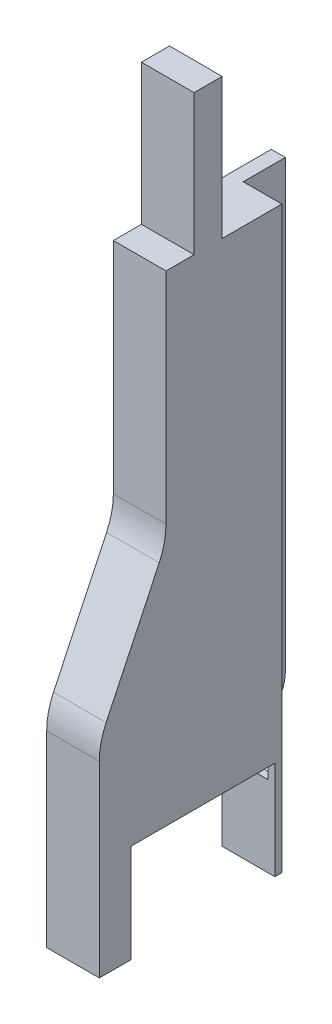
SolidWorks part; units mm, degrees
ref_plane "정면" through (0, 0, 0) normal (0, 0, 1) x (1, 0, 0)
ref_plane "윗면" through (0, 0, 0) normal (0, 1, 0) x (1, 0, 0)
ref_plane "우측면" through (0, 0, 0) normal (1, 0, 0) x (0, 0, -1)
sketch "스케치1" plane through (0, 0, 0) normal (0, 0, 1) x (1, 0, 0)
  line L0 (-318.5049, 0) -> (318.5049, 0) construction
  line L1 (0, 0) -> (0, -258.8265) construction
  line L2 (-168, 0) -> (168, 0)
  line L3 (-168, -20) -> (168, -20)
  line L4 (168, -20) -> (168, 0) construction
  line L5 (168, -20) -> (168, -340)
  line L6 (172, -340) -> (172, 0)
  line L7 (168, 0) -> (183, 0)
  line L8 (183, 0) -> (183, -340)
  line L9 (183, -340) -> (168, -340)
  line L10 (-168, -20) -> (-168, 0) construction
  line L11 (-183, -340) -> (-168, -340)
  line L12 (-183, 0) -> (-183, -340)
  line L13 (-168, 0) -> (-183, 0)
  line L14 (-172, -340) -> (-172, 0)
  line L15 (-168, -20) -> (-168, -340)
  line L16 (168, -20) -> (168, 0)
  line L17 (-168, -20) -> (-168, 0)
  point P14 (0, -20)
  dimension "D1" = 168
  dimension "D2" = 20
  dimension "D3" = 4
  dimension "D4" = 340
  dimension "D5" = 15
extrude "보스-돌출1" add sketch "스케치1" along normal blind 26 contours L3 L5 L9 L8 L7 L2 L13 L12 L11 L15
extrude "보스-돌출2" add sketch "스케치1<4>" against normal blind 19 contours L16 L5 L9 L6 L7 | L15 L17 L13 L14 L11 region at (-170, -170, 0) region at (170, -170, 0)
sketch "스케치1<4>" plane through (0, 0, 0) normal (0, 0, 1) x (1, 0, 0) same geometry as "스케치1"
fillet "필렛1" radius 10 4 edges at (-170, 0, -19) (170, 0, -19) (170, -340, -19) (-170, -340, -19)
sketch "스케치2" plane through (172, 0, 0) normal (1, 0, 0) x (0, 0, -1)
  line L0 (14, -340) -> (14, 0)
  line L1 (12, 0) -> (12, -340)
  line L4 (19, -330) -> (19, -10)
  line L5 (9, 0) -> (0, 0)
  line L6 (0, 0) -> (0, -340)
  line L7 (0, -340) -> (9, -340)
  line L8 (19, -330) -> (19, -10)
  line L9 (9, 0) -> (0, 0)
  line L10 (0, 0) -> (0, -340)
  line L11 (0, -340) -> (9, -340)
  arc A2 (19, -10) -> (9, 0) centre (9, -10) ccw
  arc A3 (9, -340) -> (19, -330) centre (9, -330) ccw
  arc A4 (19, -10) -> (9, 0) centre (9, -10) ccw
  arc A5 (9, -340) -> (19, -330) centre (9, -330) ccw
  dimension "D2" = 5
  dimension "D3" = 2
  dimension "D1" = 0
sketch "스케치3" plane through (168, 0, 0) normal (-1, 0, 0) x (0, 0, 1)
  line L0 (-12, 0) -> (-12, -340) construction
  line L1 (-14, -340) -> (-14, 0) construction
  line L2 (-12, 0) -> (-12, -340)
  line L3 (-14, -340) -> (-14, 0)
  line L4 (-19, -10) -> (-19, -330)
  line L5 (0, 0) -> (-9, 0)
  line L6 (0, -340) -> (0, 0)
  line L7 (-9, -340) -> (0, -340)
  line L8 (-19, -10) -> (-19, -330)
  line L9 (0, 0) -> (-9, 0)
  line L10 (0, -340) -> (0, 0)
  line L11 (-9, -340) -> (0, -340)
  arc A2 (-9, 0) -> (-19, -10) centre (-9, -10) ccw
  arc A3 (-19, -330) -> (-9, -340) centre (-9, -330) ccw
  arc A4 (-9, 0) -> (-19, -10) centre (-9, -10) ccw
  arc A5 (-19, -330) -> (-9, -340) centre (-9, -330) ccw
  dimension "D1" = 0
sketch "스케치5" plane through (0, 0, 0) normal (0, 1, 0) x (1, 0, 0)
  line L0 (-7, 0) -> (-7, -26)
  line L1 (7, 0) -> (7, -26)
  line L2 (-168, 0) -> (-168, -6)
  line L3 (-168, -6) -> (-7, -6)
  line L4 (7, -6) -> (168, -6)
  line L5 (168, -6) -> (168, 0)
  line L12 (-168, 0) -> (-168, 9)
  line L13 (-168, 9) -> (-172, 9)
  line L14 (-172, 9) -> (-172, 0)
  line L15 (-172, 0) -> (-183, 0)
  line L16 (-183, 0) -> (-183, -26)
  line L17 (-183, -26) -> (183, -26)
  line L18 (183, -26) -> (183, 0)
  line L19 (183, 0) -> (172, 0)
  line L20 (172, 0) -> (172, 9)
  line L21 (172, 9) -> (168, 9)
  line L22 (168, 9) -> (168, 0)
  line L23 (168, 0) -> (-168, 0)
  line L24 (-168, 0) -> (-168, 9)
  line L25 (-168, 9) -> (-172, 9)
  line L26 (-172, 9) -> (-172, 0)
  line L27 (-172, 0) -> (-183, 0)
  line L28 (-183, 0) -> (-183, -26)
  line L29 (-183, -26) -> (183, -26)
  line L30 (183, -26) -> (183, 0)
  line L31 (183, 0) -> (172, 0)
  line L32 (172, 0) -> (172, 9)
  line L33 (172, 9) -> (168, 9)
  line L34 (168, 9) -> (168, 0)
  line L35 (168, 0) -> (-168, 0)
  line M27 (168, 0) -> (-168, 0)
  dimension "D2" = 7
  dimension "D3" = 7
  dimension "D4" = 6
  dimension "D1" = 0
extrude "컷-돌출1" cut sketch "스케치5" against normal blind 52 contours L2 L3 L0 M27 | L4 L5 L1 M27 region at (-87.5, 0, 3) region at (87.5, 0, 3)
extrude "보스-돌출4" add sketch "스케치1<5>" against normal blind 7 contours L9 L8 L7 L6 | L11 L14 L13 L12 region at (-177.5, -170, 0) region at (177.5, -170, 0)
sketch "스케치1<5>" plane through (0, 0, 0) normal (0, 0, 1) x (1, 0, 0) same geometry as "스케치1"
sketch "스케치6" plane through (0, -340, 0) normal (0, -1, 0) x (1, 0, 0)
  line L0 (-172, -7) -> (-126.7636, -7) construction
  line L1 (-172, -7) -> (-168, -7)
  line L2 (-168, -7) -> (-168, -5)
  line L3 (-168, -5) -> (-174.5, -5)
  line L4 (-174.5, -5) -> (-174.5, -7)
  line L5 (-181.1, -7) -> (-181.1, -5)
  line L6 (-172, -7) -> (-172, -9)
  line L7 (-172, -9) -> (-168, -9)
  line L8 (-168, -9) -> (-168, 26)
  line L9 (-168, 26) -> (-183, 26)
  line L10 (-183, 26) -> (-183, -7)
  line L11 (-183, -7) -> (-172, -7)
  line L12 (-172, -7) -> (-172, -9)
  line L13 (-172, -9) -> (-168, -9)
  line L14 (-168, -9) -> (-168, 26)
  line L15 (-168, 26) -> (-183, 26)
  line L16 (-183, 26) -> (-183, -7)
  line L17 (-183, -7) -> (-172, -7)
  line L18 (-181.1, -5) -> (-183, -5)
  line L19 (-181.1, -5) -> (-174.5, -5)
  line L20 (-168, 26) -> (-168, 36)
  line L21 (-168, 36) -> (-183, 36)
  line L22 (-183, 36) -> (-183, 26)
  line L23 (-168, 36) -> (-168, 45)
  line L24 (-168, 45) -> (-183, 45)
  line L25 (-183, 45) -> (-183, 36)
  line M14 (-168, -9) -> (-168, 26)
  line M15 (-168, 26) -> (-183, 26)
  line M17 (-183, -7) -> (-172, -7)
  dimension "D2" = 6.5
  dimension "D3" = 2
  dimension "D4" = 6.6
  dimension "D5" = 41
  dimension "D6" = 9
  dimension "D1" = 0
extrude "보스-돌출5" add sketch "스케치6" along normal blind 28 contours L5 L18 L16 M17 | L19 L5 L4 M17 | L3 L4 L1 M17 M14 region at (-171.25, -340, -6) region at (-177.8, -340, -6) region at (-182.05, -340, -6)
extrude "컷-돌출2" cut sketch "스케치6<3>" along normal blind 5 contours L19 L5 L4 M17 region at (-177.8, -340, -6)
sketch "스케치6<3>" plane through (0, -340, 0) normal (0, -1, 0) x (1, 0, 0) same geometry as "스케치6"
fillet "필렛2" radius 20 1 edges at (-170, -340, -7)
extrude "보스-돌출6" add sketch "스케치6<4>" against normal blind 30 contours L21 L22 L20 M15 | L24 L25 L21 L23 region at (-175.5, -340, 31) region at (-175.5, -340, 40.5)
sketch "스케치6<4>" plane through (0, -340, 0) normal (0, -1, 0) x (1, 0, 0) same geometry as "스케치6"
extrude "보스-돌출7" add sketch "스케치6<5>" along normal blind 28 contours L24 L25 L21 L23 region at (-175.5, -340, 40.5)
sketch "스케치6<5>" plane through (0, -340, 0) normal (0, -1, 0) x (1, 0, 0) same geometry as "스케치6"
sketch "스케치9" plane through (-183, 0, 0) normal (-1, 0, 0) x (0, 0, 1)
  line L0 (45, -310) -> (26, -270)
  line L1 (26, 0) -> (26, -310) construction
  line L12 (26, 0) -> (-7, 0)
  line L13 (-7, 0) -> (-7, -368)
  line L14 (-7, -368) -> (-5, -368)
  line L15 (-5, -368) -> (-5, -340)
  line L16 (-5, -340) -> (36, -340)
  line L17 (36, -340) -> (36, -368)
  line L18 (36, -368) -> (45, -368)
  line L19 (45, -368) -> (45, -310)
  line L20 (45, -310) -> (26, -310)
  line L21 (26, -310) -> (26, 0)
  line L22 (26, 0) -> (-7, 0)
  line L23 (-7, 0) -> (-7, -368)
  line L24 (-7, -368) -> (-5, -368)
  line L25 (-5, -368) -> (-5, -340)
  line L26 (-5, -340) -> (36, -340)
  line L27 (36, -340) -> (36, -368)
  line L28 (36, -368) -> (45, -368)
  line L29 (45, -368) -> (45, -310)
  line L30 (45, -310) -> (26, -310)
  line L31 (26, -310) -> (26, 0)
  line M19 (45, -310) -> (26, -310)
  line M20 (26, -310) -> (26, 0)
  dimension "D2" = 40
  dimension "D1" = 0
extrude "보스-돌출8" add sketch "스케치9" against normal blind 15 contours L0 M19 M20 region at (-183, -296.6667, 32.3333)
fillet "필렛3" radius 20 2 edges at (-175.5, -270, 26) (-175.5, -310, 45)
mirror "대칭 복사2" about plane through (0, 0, 0) normal (1, 0, 0) of "보스-돌출5", "컷-돌출2", "필렛3", "보스-돌출6", "보스-돌출7", "보스-돌출8"
fillet "필렛4" radius 20 1 edges at (170, -340, -7)
sketch "스케치10" plane through (183, 0, 0) normal (1, 0, 0) x (0, 0, -1)
  line L0 (-27.9344, -274.0725) -> (-43.0656, -305.9275) construction
  line L1 (-45, -314.5086) -> (-45, -368) construction
  line L2 (-45, -368) -> (-36, -368) construction
  line L3 (-36, -368) -> (-36, -340) construction
  line L4 (-36, -340) -> (5, -340) construction
  line L5 (5, -340) -> (5, -368) construction
  line L6 (5, -368) -> (7, -368) construction
  line L7 (7, -368) -> (7, -354) construction
  line L8 (19, -330) -> (19, -10) construction
  line L9 (9, 0) -> (-6, 0) construction
  line L10 (-6, 0) -> (-6, -20) construction
  line L11 (-6, -20) -> (-26, -20) construction
  line L12 (-26, -20) -> (-26, -265.4914) construction
  line L13 (-27.9344, -274.0725) -> (-43.0656, -305.9275) construction
  line L14 (-45, -314.5086) -> (-45, -368) construction
  line L15 (-45, -368) -> (-36, -368) construction
  line L16 (-36, -368) -> (-36, -340) construction
  line L17 (-36, -340) -> (5, -340) construction
  line L18 (5, -340) -> (5, -368) construction
  line L19 (5, -368) -> (7, -368) construction
  line L20 (7, -368) -> (7, 0) construction
  line L21 (7, 0) -> (-26, 0) construction
  line L22 (-26, 0) -> (-26, -265.4914) construction
  line L23 (-27.9344, -274.0725) -> (-43.0656, -305.9275)
  line L24 (-45, -314.5086) -> (-45, -368)
  line L25 (-45, -368) -> (-36, -368)
  line L26 (-36, -368) -> (-36, -340)
  line L27 (-36, -340) -> (5, -340)
  line L28 (5, -340) -> (5, -368)
  line L29 (5, -368) -> (7, -368)
  line L30 (7, -368) -> (7, -354)
  line L31 (19, -330) -> (19, -10)
  line L32 (9, 0) -> (-6, 0)
  line L33 (-6, 0) -> (-6, -20)
  line L34 (-6, -20) -> (-26, -20)
  line L35 (-26, -20) -> (-26, -265.4914)
  line L36 (-27.9344, -274.0725) -> (-43.0656, -305.9275)
  line L37 (-45, -314.5086) -> (-45, -368)
  line L38 (-45, -368) -> (-36, -368)
  line L39 (-36, -368) -> (-36, -340)
  line L40 (-36, -340) -> (5, -340)
  line L41 (5, -340) -> (5, -368)
  line L42 (5, -368) -> (7, -368)
  line L43 (7, -368) -> (7, 0)
  line L44 (7, 0) -> (-26, 0)
  line L45 (-26, 0) -> (-26, -265.4914)
  line L46 (-26, -10) -> (-6, -10)
  arc A0 (-43.0656, -305.9275) -> (-45, -314.5086) centre (-25, -314.5086) ccw construction
  arc A1 (15, -338) -> (7, -354) centre (27, -354) ccw construction
  arc A2 (15, -338) -> (19, -330) centre (9, -330) ccw construction
  arc A3 (19, -10) -> (9, 0) centre (9, -10) ccw construction
  arc A4 (-27.9344, -274.0725) -> (-26, -265.4914) centre (-46, -265.4914) ccw construction
  arc A5 (-43.0656, -305.9275) -> (-45, -314.5086) centre (-25, -314.5086) ccw construction
  arc A6 (-27.9344, -274.0725) -> (-26, -265.4914) centre (-46, -265.4914) ccw construction
  arc A7 (-43.0656, -305.9275) -> (-45, -314.5086) centre (-25, -314.5086) ccw
  arc A8 (15, -338) -> (7, -354) centre (27, -354) ccw
  arc A9 (15, -338) -> (19, -330) centre (9, -330) ccw
  arc A10 (19, -10) -> (9, 0) centre (9, -10) ccw
  arc A11 (-27.9344, -274.0725) -> (-26, -265.4914) centre (-46, -265.4914) ccw
  arc A12 (-43.0656, -305.9275) -> (-45, -314.5086) centre (-25, -314.5086) ccw
  arc A13 (-27.9344, -274.0725) -> (-26, -265.4914) centre (-46, -265.4914) ccw
sketch "스케치11" plane through (168, 0, 0) normal (-1, 0, 0) x (0, 0, 1)
  line L10 (43.0656, -305.9275) -> (27.9344, -274.0725)
  line L11 (45, -368) -> (45, -314.5086)
  line L12 (36, -368) -> (45, -368)
  line L13 (45, -368) -> (45, -314.5086)
  line L14 (43.0656, -305.9275) -> (27.9344, -274.0725)
  line L15 (26, -265.4914) -> (26, -20)
  line L16 (26, -20) -> (6, -20)
  line L17 (6, -20) -> (6, 0)
  line L18 (6, 0) -> (-9, 0)
  line L19 (-19, -10) -> (-19, -330)
  line L20 (-7, -354) -> (-7, -368)
  line L21 (-7, -368) -> (-5, -368)
  line L22 (-5, -368) -> (-5, -340)
  line L23 (-5, -340) -> (36, -340)
  line L24 (36, -340) -> (36, -368)
  line L25 (36, -368) -> (45, -368)
  line L26 (45, -368) -> (45, -314.5086)
  line L27 (43.0656, -305.9275) -> (27.9344, -274.0725)
  line L28 (26, -265.4914) -> (26, -20)
  line L29 (26, -20) -> (6, -20)
  line L30 (6, -20) -> (6, 0)
  line L31 (6, 0) -> (-9, 0)
  line L32 (-19, -10) -> (-19, -330)
  line L33 (-7, -354) -> (-7, -368)
  line L34 (-7, -368) -> (-5, -368)
  line L35 (-5, -368) -> (-5, -340)
  line L36 (-5, -340) -> (36, -340)
  line L37 (36, -340) -> (36, -368)
  line L38 (36, -368) -> (45, -368)
  line L39 (36, -340) -> (36, -368)
  line L40 (-5, -340) -> (36, -340)
  line L41 (-5, -368) -> (-5, -340)
  line L42 (-7, -368) -> (-5, -368)
  line L43 (-7, 0) -> (-7, -368)
  line L44 (26, 0) -> (-7, 0)
  line L45 (26, -265.4914) -> (26, 0)
  line L46 (43.0656, -305.9275) -> (27.9344, -274.0725)
  line L47 (45, -368) -> (45, -314.5086)
  line L48 (36, -368) -> (45, -368)
  line L49 (36, -340) -> (36, -368)
  line L50 (-5, -340) -> (36, -340)
  line L51 (-5, -368) -> (-5, -340)
  line L52 (-7, -368) -> (-5, -368)
  line L53 (-7, 0) -> (-7, -368)
  line L54 (26, 0) -> (-7, 0)
  line L55 (26, -265.4914) -> (26, 0)
  arc A2 (45, -314.5086) -> (43.0656, -305.9275) centre (25, -314.5086) ccw
  arc A3 (26, -265.4914) -> (27.9344, -274.0725) centre (46, -265.4914) ccw
  arc A4 (45, -314.5086) -> (43.0656, -305.9275) centre (25, -314.5086) ccw
  arc A5 (45, -314.5086) -> (43.0656, -305.9275) centre (25, -314.5086) ccw
  arc A6 (26, -265.4914) -> (27.9344, -274.0725) centre (46, -265.4914) ccw
  arc A7 (-9, 0) -> (-19, -10) centre (-9, -10) ccw
  arc A8 (-19, -330) -> (-15, -338) centre (-9, -330) ccw
  arc A9 (-7, -354) -> (-15, -338) centre (-27, -354) ccw
  arc A10 (45, -314.5086) -> (43.0656, -305.9275) centre (25, -314.5086) ccw
  arc A11 (26, -265.4914) -> (27.9344, -274.0725) centre (46, -265.4914) ccw
  arc A12 (-9, 0) -> (-19, -10) centre (-9, -10) ccw
  arc A13 (-19, -330) -> (-15, -338) centre (-9, -330) ccw
  arc A14 (-7, -354) -> (-15, -338) centre (-27, -354) ccw
  arc A15 (26, -265.4914) -> (27.9344, -274.0725) centre (46, -265.4914) ccw
  line M31 (45, -368) -> (45, -314.5086)
  arc M32 (45, -314.5086) -> (43.0656, -305.9275) centre (25, -314.5086) ccw
  line M33 (43.0656, -305.9275) -> (27.9344, -274.0725)
  arc M34 (27.9344, -274.0725) -> (26, -265.4914) centre (46, -265.4914) cw
  line M35 (26, -265.4914) -> (26, -20)
  line M36 (26, -20) -> (6, -20)
  line M37 (6, -20) -> (6, 0)
  line M38 (6, 0) -> (-9, 0)
  arc M39 (-9, 0) -> (-19, -10) centre (-9, -10) ccw
  line M40 (-19, -10) -> (-19, -330)
  arc M41 (-19, -330) -> (-15, -338) centre (-9, -330) ccw
  arc M42 (-15, -338) -> (-7, -354) centre (-27, -354) cw
  line M43 (-7, -354) -> (-7, -368)
  line M44 (-7, -368) -> (-5, -368)
  line M45 (-5, -368) -> (-5, -340)
  line M46 (-5, -340) -> (36, -340)
  line M47 (36, -340) -> (36, -368)
  line M48 (36, -368) -> (45, -368)
  dimension "D1" = 0
  dimension "D2" = 0
extrude "컷-돌출3" cut sketch "스케치11" along normal blind 617 contours L53 M38 M43 M44 M45 M46 M47 M48 M31 M32 M33 M34 M35 M36 M37 | L55 L54 M36 M37 | L53 L31 M39 M40 M41 M42 region at (168, -191.2863, 11.8028) region at (168, -10, 16) region at (168, -171.1237, -12.9334)
extrude "컷-돌출4" cut sketch "스케치10" against normal blind 617 contours L46 L45 L34 L33 region at (183, -15, 16)
sketch "스케치12" plane through (168, 0, 0) normal (-1, 0, 0) x (0, 0, 1)
  line L0 (18, -203) -> (18, -163)
  line L1 (18, -163) -> (10, -163)
  line L2 (10, -163) -> (10, -203)
  line L3 (10, -203) -> (-19, -203)
  line L4 (18.5, -203) -> (18.5, -162.5)
  line L5 (18.5, -162.5) -> (9.5, -162.5)
  line L6 (9.5, -162.5) -> (9.5, -203)
  line L15 (26, -183) -> (-19, -183) construction
  line L16 (26, -203) -> (18, -203)
  line L18 (-7, 0) -> (-9, 0)
  line L19 (-7, -354) -> (-7, 0)
  line L20 (-19, -10) -> (-19, -330)
  line L21 (-7, 0) -> (-9, 0)
  line L22 (-7, -354) -> (-7, 0)
  line L23 (-19, -10) -> (-19, -330)
  line L30 (6, -10) -> (26, -10)
  line L31 (26, -10) -> (26, 0)
  line L32 (26, 0) -> (-9, 0)
  line L33 (-19, -10) -> (-19, -330)
  line L34 (-7, -354) -> (-7, -368)
  line L35 (-7, -368) -> (-5, -368)
  line L36 (-5, -368) -> (-5, -340)
  line L37 (-5, -340) -> (36, -340)
  line L38 (36, -340) -> (36, -368)
  line L39 (36, -368) -> (45, -368)
  line L40 (45, -368) -> (45, -314.5086)
  line L41 (43.0656, -305.9275) -> (27.9344, -274.0725)
  line L42 (26, -265.4914) -> (26, -20)
  line L43 (26, -20) -> (6, -20)
  line L44 (6, -20) -> (6, -10)
  line L45 (6, -10) -> (26, -10)
  line L46 (26, -10) -> (26, 0)
  line L47 (26, 0) -> (-9, 0)
  line L48 (-19, -10) -> (-19, -330)
  line L49 (-7, -354) -> (-7, -368)
  line L50 (-7, -368) -> (-5, -368)
  line L51 (-5, -368) -> (-5, -340)
  line L52 (-5, -340) -> (36, -340)
  line L53 (36, -340) -> (36, -368)
  line L54 (36, -368) -> (45, -368)
  line L55 (45, -368) -> (45, -314.5086)
  line L56 (43.0656, -305.9275) -> (27.9344, -274.0725)
  line L57 (26, -265.4914) -> (26, -20)
  line L58 (26, -20) -> (6, -20)
  line L59 (6, -20) -> (6, -10)
  arc A8 (-7, -354) -> (-15, -338) centre (-27, -354) ccw
  arc A9 (-19, -330) -> (-15, -338) centre (-9, -330) ccw
  arc A10 (-9, 0) -> (-19, -10) centre (-9, -10) ccw
  arc A11 (-19, -330) -> (-15, -338) centre (-9, -330) ccw
  arc A12 (-7, -354) -> (-15, -338) centre (-27, -354) ccw
  arc A13 (45, -314.5086) -> (43.0656, -305.9275) centre (25, -314.5086) ccw
  arc A14 (26, -265.4914) -> (27.9344, -274.0725) centre (46, -265.4914) ccw
  arc A15 (-9, 0) -> (-19, -10) centre (-9, -10) ccw
  arc A16 (-19, -330) -> (-15, -338) centre (-9, -330) ccw
  arc A17 (-7, -354) -> (-15, -338) centre (-27, -354) ccw
  arc A18 (45, -314.5086) -> (43.0656, -305.9275) centre (25, -314.5086) ccw
  arc A19 (26, -265.4914) -> (27.9344, -274.0725) centre (46, -265.4914) ccw
  arc A20 (-9, 0) -> (-19, -10) centre (-9, -10) ccw
  arc A21 (-7, -354) -> (-15, -338) centre (-27, -354) ccw
  arc A22 (-19, -330) -> (-15, -338) centre (-9, -330) ccw
  arc A23 (-9, 0) -> (-19, -10) centre (-9, -10) ccw
  line M31 (6, -10) -> (26, -10)
  line M32 (26, -10) -> (26, 0)
  line M33 (26, 0) -> (-9, 0)
  arc M34 (-9, 0) -> (-19, -10) centre (-9, -10) ccw
  line M35 (-19, -10) -> (-19, -330)
  line M48 (26, -265.4914) -> (26, -20)
  line M49 (26, -20) -> (6, -20)
  line M50 (6, -20) -> (6, -10)
  dimension "D3" = 185
  dimension "D4" = 8
  dimension "D5" = 8
  dimension "D6" = 20
  dimension "D7" = 20
  dimension "D1" = 0
  dimension "D2" = 0
  dimension "D8" = 0.5
extrude "컷-돌출6" cut sketch "스케치12" against normal blind 37 contours L15 L57 L22 L6 L5 L4 M49 M50 M31 M32 M33 | L15 L4 L16 M48 | L4 L15 L0 L16 | L2 L15 L6 L3 | L15 L4 L5 L6 L2 L1 L0 | L6 L15 L22 L3 | L15 L22 M33 M34 M35 | L22 L15 L48 L3 region at (168, -193, 18.25) region at (168, -173, 18.2239) region at (168, -193, 22.25) region at (168, -91.5547, 9.1233) region at (168, -193, 9.75) region at (168, -193, 1.25) region at (168, -193, -13) region at (168, -92.381, -12.9628)
